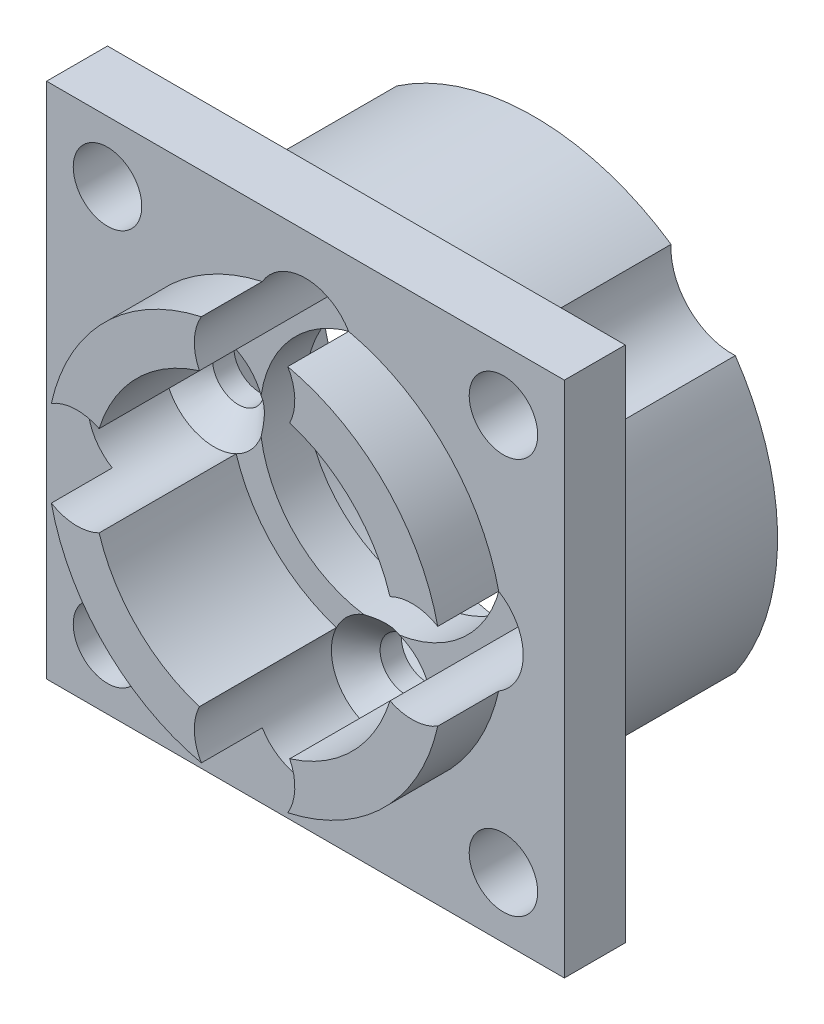
SolidWorks part; units mm, degrees
material "1060 合金"
ref_plane "前视基准面" through (0, 0, 0) normal (0, 0, 1) x (1, 0, 0)
ref_plane "上视基准面" through (0, 0, 0) normal (0, 1, 0) x (1, 0, 0)
ref_plane "右视基准面" through (0, 0, 0) normal (1, 0, 0) x (0, 0, -1)
sketch "草图1" plane through (0, 0, 0) normal (1, 0, 0) x (0, 0, -1)
  line L0 (0, 0) -> (85.2801, 0) construction
  line L1 (0, 0) -> (0, 40.8583) construction
  line L2 (0, 13) -> (0, 10)
  line L3 (0, 10) -> (9, 10)
  line L4 (9, 10) -> (9, 8)
  line L5 (9, 8) -> (12, 8)
  line L6 (12, 8) -> (12, 14)
  line L7 (12, 14) -> (19, 14)
  line L8 (19, 14) -> (19, 16)
  line L9 (19, 16) -> (4, 16)
  line L10 (0, 13) -> (4, 13)
  line L11 (4, 13) -> (4, 16)
  dimension "D1" = 8
  dimension "D2" = 3
  dimension "D3" = 13
  dimension "D4" = 14
  dimension "D5" = 2
  dimension "D6" = 7
  dimension "D7" = 4
  dimension "D8" = 8
  dimension "D9" = 10
revolve "旋转1" add sketch "草图1" angle 360 about L0
hole_wizard "打孔尺寸根据十字槽沉头木螺钉的类型1" positions "草图3" profile "草图2" countersink size "M3" standard "GB" end condition through all
sketch "草图3" plane through (0, 0, 0) normal (0, 0, 1) x (1, 0, 0)
  circle A0 centre (0, 0) radius 11 construction
  point P0 (0, 11)
  point P12 (11, 0)
  point P13 (0, -11)
  point P14 (-11, 0)
  dimension "D1" = 22
  dimension "D2" = 4
sketch "草图2" plane through (0, 11, 0) normal (1, 0, 0) x (0, -1, 0)
  line L0 (0, 0) -> (0, 19)
  line L1 (0, 19) -> (1.7, 19)
  line L2 (1.7, 19) -> (1.7, 10.6)
  line L3 (1.7, 10.6) -> (3.3, 9)
  line L4 (3.3, 9) -> (3.3, 0)
  line L6 (3.3, 0) -> (0, 0)
  line L7 (-1.7, 10.6) -> (-3.3, 9) construction
  line L11 (0, -6.35) -> (0, 107.95) construction
  dimension "通孔孔直径" = 3.4
  dimension "通孔孔深度" = 19
  dimension "锥形沉头孔直径" = 6.6
  dimension "锥形沉头孔角度" = 90
  dimension "头间隙" = 9
sketch "草图4" plane through (0, 0, -4) normal (0, 0, 1) x (1, 0, 0)
  line L1 (-17, -17) -> (17, -17)
  line L2 (-17, -17) -> (-17, 17)
  line L3 (-17, 17) -> (17, 17)
  line L4 (17, -17) -> (17, 17)
  line L5 (-17, -17) -> (17, 17) construction
  line L6 (-17, 17) -> (17, -17) construction
  circle A0 centre (0, 0) radius 16
  circle A1 centre (0, 0) radius 16 construction
  point P0 (0, 0)
  dimension "D1" = 34
extrude "凸台-拉伸1" add sketch "草图4" against normal blind 4
hole_wizard "打孔尺寸根据内六角圆柱头螺钉的类型2" positions "草图10" profile "草图9" counterbore size "M4" standard "GB" end condition through all
sketch "草图10" plane through (0, 0, -19) normal (0, 0, -1) x (-1, 0, 0)
  line L0 (0, 0) -> (17, 17) construction
  line L2 (17, 17) -> (17, -17) construction
  point P0 (13, 13)
  point P26 (13, -13)
  point P27 (-13, -13)
  point P28 (-13, 13)
  dimension "D1" = 4
  dimension "D2" = 4
sketch "草图9" plane through (-13, 13, -19) normal (1, 0, 0) x (0, 1, 0)
  line L0 (0, 0) -> (0, 19)
  line L1 (0, 19) -> (2.25, 19)
  line L3 (2.25, 19) -> (2.25, 11)
  line L4 (2.25, 11) -> (4, 11)
  line L5 (4, 11) -> (4, 0)
  line L7 (4, 0) -> (0, 0)
  line L11 (0, -6.35) -> (0, 107.95) construction
  dimension "通孔孔直径" = 4.5
  dimension "通孔孔深度" = 19
  dimension "柱形沉头孔直径" = 8
  dimension "柱形沉头孔深度" = 11
